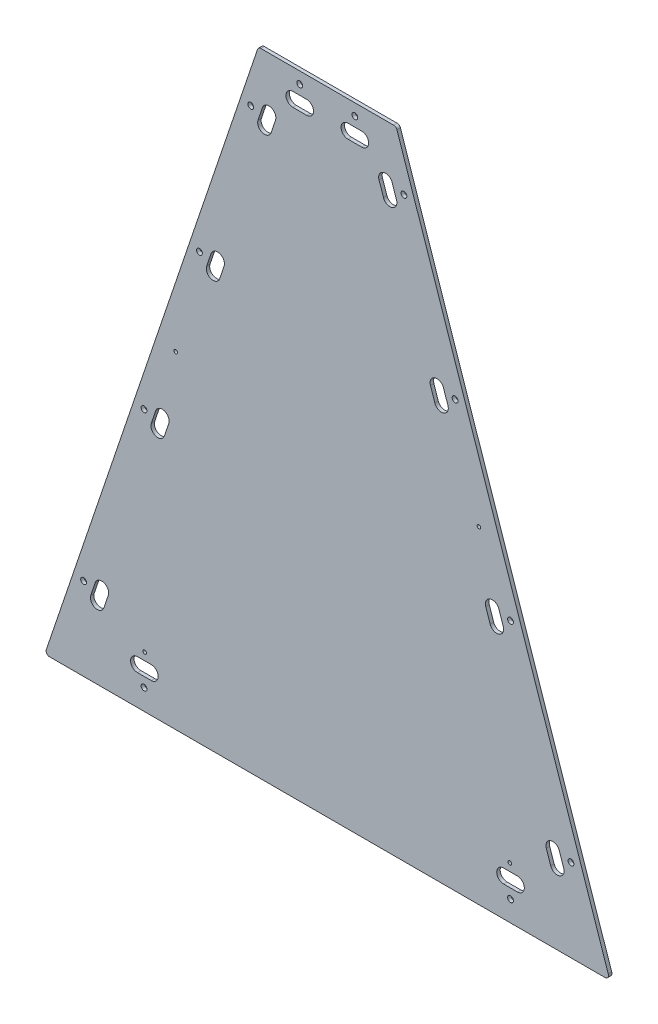
SolidWorks part; units mm, degrees
material "PC High Viscosity"
ref_plane "Front Plane" through (0, 0, 0) normal (0, 0, 1) x (1, 0, 0)
ref_plane "Top Plane" through (0, 0, 0) normal (0, 1, 0) x (1, 0, 0)
ref_plane "Right Plane" through (0, 0, 0) normal (1, 0, 0) x (0, 0, -1)
sketch "Sketch1" plane through (0, 0, 0) normal (0, 0, 1) x (1, 0, 0)
  line L0 (128.5466, 292.9716) -> (382.5466, 292.9716)
  line L5 (382.5466, 292.9716) -> (776.2466, -872.6346)
  line L6 (776.2466, -872.6346) -> (-265.1534, -872.6346)
  line L7 (-265.1534, -872.6346) -> (128.5466, 292.9716)
  line L8 (-168.2075, -740.392) -> (-160.0795, -716.3277) construction
  line L9 (-180.2397, -736.328) -> (-172.1116, -712.2636)
  line L10 (-156.1753, -744.4561) -> (-148.0473, -720.3917)
  line L11 (-94.2317, -804.0546) -> (-68.8317, -804.0546) construction
  line L12 (-94.2317, -791.3546) -> (-68.8317, -791.3546)
  line L13 (-94.2317, -816.7546) -> (-68.8317, -816.7546)
  line L14 (580.5201, -804.0546) -> (605.9201, -804.0546) construction
  line L15 (580.5201, -791.3546) -> (605.9201, -791.3546)
  line L16 (580.5201, -816.7546) -> (605.9201, -816.7546)
  line L17 (-56.7399, -410.3759) -> (-48.6118, -386.3115) construction
  line L18 (-68.7721, -406.3118) -> (-60.644, -382.2474)
  line L19 (-44.7077, -414.4399) -> (-36.5796, -390.3755)
  line L20 (45.2346, -108.4656) -> (53.3626, -84.4012) construction
  line L21 (33.2024, -104.4015) -> (41.3305, -80.3372)
  line L22 (57.2668, -112.5296) -> (65.3948, -88.4652)
  line L29 (139.9814, 172.0464) -> (148.1095, 196.1108) construction
  line L30 (127.9493, 176.1104) -> (136.0773, 200.1748)
  line L31 (152.0136, 167.9823) -> (160.1417, 192.0467)
  line L32 (192.1135, 241.2472) -> (217.5135, 241.2472) construction
  line L33 (192.1135, 253.9472) -> (217.5135, 253.9472)
  line L34 (192.1135, 228.5472) -> (217.5135, 228.5472)
  line L35 (293.6466, 241.2472) -> (319.0466, 241.2472) construction
  line L36 (293.6466, 253.9472) -> (319.0466, 253.9472)
  line L37 (293.6466, 228.5472) -> (319.0466, 228.5472)
  line L38 (371.0972, 172.0897) -> (362.9691, 196.154) construction
  line L39 (359.065, 168.0256) -> (350.9369, 192.09)
  line L40 (383.1294, 176.1537) -> (375.0013, 200.2181)
  line L41 (465.8587, -108.4656) -> (457.7306, -84.4012) construction
  line L42 (453.8265, -112.5296) -> (445.6984, -88.4652)
  line L43 (477.8909, -104.4015) -> (469.7628, -80.3372)
  line L44 (679.3008, -740.392) -> (671.1727, -716.3277) construction
  line L47 (567.8332, -410.3759) -> (559.7051, -386.3115) construction
  line L48 (555.801, -414.4399) -> (547.6729, -390.3755)
  line L49 (579.8654, -406.3118) -> (571.7373, -382.2474)
  line L50 (667.2686, -744.4561) -> (659.1405, -720.3917)
  line L53 (691.333, -736.328) -> (683.2049, -712.2636)
  circle A0 centre (396.7562, 191.3716) radius 5.3578
  circle A1 centre (114.6592, 192.3252) radius 5.3578
  circle A2 centre (-193.5708, -720.2346) radius 5.3578
  circle A4 centre (704.6641, -720.2346) radius 5.3578
  circle A5 centre (491.1275, -88.0284) radius 5.3578
  circle A6 centre (593.2201, -390.2884) radius 5.3578
  circle A7 centre (19.9658, -88.0284) radius 5.3578
  circle A8 centre (-82.1268, -390.2884) radius 5.3578
  circle A9 centre (306.3466, 271.7272) radius 5.3578
  circle A10 centre (204.7466, 271.7272) radius 5.3578
  circle A12 centre (-82.1268, -834.5346) radius 5.3578
  circle A13 centre (593.2201, -834.5346) radius 5.3578
  arc A14 (-180.2397, -736.328) -> (-156.1753, -744.4561) centre (-168.2075, -740.392) ccw
  arc A15 (-148.0473, -720.3917) -> (-172.1116, -712.2636) centre (-160.0795, -716.3277) ccw
  arc A16 (-94.2317, -791.3546) -> (-94.2317, -816.7546) centre (-94.2317, -804.0546) ccw
  arc A17 (-68.8317, -816.7546) -> (-68.8317, -791.3546) centre (-68.8317, -804.0546) ccw
  arc A18 (580.5201, -791.3546) -> (580.5201, -816.7546) centre (580.5201, -804.0546) ccw
  arc A19 (605.9201, -816.7546) -> (605.9201, -791.3546) centre (605.9201, -804.0546) ccw
  arc A20 (-68.7721, -406.3118) -> (-44.7077, -414.4399) centre (-56.7399, -410.3759) ccw
  arc A21 (-36.5796, -390.3755) -> (-60.644, -382.2474) centre (-48.6118, -386.3115) ccw
  arc A22 (33.2024, -104.4015) -> (57.2668, -112.5296) centre (45.2346, -108.4656) ccw
  arc A23 (65.3948, -88.4652) -> (41.3305, -80.3372) centre (53.3626, -84.4012) ccw
  arc A28 (127.9493, 176.1104) -> (152.0136, 167.9823) centre (139.9814, 172.0464) ccw
  arc A29 (160.1417, 192.0467) -> (136.0773, 200.1748) centre (148.1095, 196.1108) ccw
  arc A30 (192.1135, 253.9472) -> (192.1135, 228.5472) centre (192.1135, 241.2472) ccw
  arc A31 (217.5135, 228.5472) -> (217.5135, 253.9472) centre (217.5135, 241.2472) ccw
  arc A32 (293.6466, 253.9472) -> (293.6466, 228.5472) centre (293.6466, 241.2472) ccw
  arc A33 (319.0466, 228.5472) -> (319.0466, 253.9472) centre (319.0466, 241.2472) ccw
  arc A34 (359.065, 168.0256) -> (383.1294, 176.1537) centre (371.0972, 172.0897) ccw
  arc A35 (375.0013, 200.2181) -> (350.9369, 192.09) centre (362.9691, 196.154) ccw
  arc A36 (453.8265, -112.5296) -> (477.8909, -104.4015) centre (465.8587, -108.4656) ccw
  arc A37 (469.7628, -80.3372) -> (445.6984, -88.4652) centre (457.7306, -84.4012) ccw
  arc A40 (555.801, -414.4399) -> (579.8654, -406.3118) centre (567.8332, -410.3759) ccw
  arc A41 (571.7373, -382.2474) -> (547.6729, -390.3755) centre (559.7051, -386.3115) ccw
  arc A44 (667.2686, -744.4561) -> (691.333, -736.328) centre (679.3008, -740.392) ccw
  arc A45 (683.2049, -712.2636) -> (659.1405, -720.3917) centre (671.1727, -716.3277) ccw
  point P24 (-164.1435, -728.3598)
  point P35 (0, 0)
  point P39 (-81.5317, -804.0546)
  point P47 (593.2201, -804.0546)
  point P56 (-52.6759, -398.3437)
  point P62 (204.8135, 241.2472)
  point P65 (49.2986, -96.4334)
  point P93 (144.0455, 184.0786)
  point P106 (306.3466, 241.2472)
  point P115 (367.0332, 184.1219)
  point P125 (461.7947, -96.4334)
  point P136 (675.2368, -728.3598)
  point P140 (563.7691, -398.3437)
  dimension "D5" = 10.7156
  dimension "D6" = 19.05
  dimension "D7" = 17.78
  dimension "D8" = 17.78
  dimension "D9" = 17.78
  dimension "D10" = 17.78
  dimension "D11" = 17.78
  dimension "D12" = 17.78
  dimension "D13" = 38.1
  dimension "D31" = 183.6216
  dimension "D32" = 144.2748
  dimension "D36" = 108.893
  dimension "D37" = 17.78
  dimension "D41" = 76.2669
  dimension "D34" = 776.2012
  dimension "D35" = 25.4
  dimension "D1" = 254
  dimension "D2" = 1230.2998
  dimension "D3" = 1230.2998
  dimension "D4" = 1041.4
  dimension "D14" = 19.05
  dimension "D15" = 683.26
  dimension "D16" = 19.05
  dimension "D17" = 76.2
  dimension "D18" = 381
  dimension "D19" = 683.26
  dimension "D20" = 152.4
  dimension "D21" = 152.4
  dimension "D22" = 19.05
  dimension "D23" = 76.2
  dimension "D24" = 19.05
  dimension "D25" = 381
  dimension "D26" = 101.6
  dimension "D27" = 19.05
  dimension "D28" = 19.05
  dimension "D29" = 19.05
  dimension "D30" = 101.6
  dimension "D33" = 474.291
  dimension "D38" = 38.1
  dimension "D39" = 25.4
  dimension "D40" = 17.78
  dimension "D42" = 17.78
  dimension "D43" = 108.8497
  dimension "D47" = 17.78
  dimension "D52" = 17.78
  dimension "D53" = 17.78
  dimension "D56" = 21.2444
  dimension "D57" = 21.2444
extrude "Boss-Extrude1" add sketch "Sketch1" along normal blind 6.35 contours L7 L6 L5 L0 A29 L31 A28 L30 A23 L22 A22 L21 A21 L19 A20 L18 A19 L16 A18 L15 A17 L13 A16 L12 A15 L10 A14 L9 A13 A12 A10 A9 A8 A7 A6 A5 region at (255.5456, -410.7622, 0)
fillet "Fillet1" radius 6.35 4 edges at (-265.1534, -872.6346, 3.175) (776.2466, -872.6346, 3.175) (382.5466, 292.9716, 3.175) (128.5466, 292.9716, 3.175)
sketch "Sketch2" plane through (0, 0, 6.35) normal (0, 0, 1) x (1, 0, 0)
  line L0 (255.5466, -872.6346) -> (255.5466, 292.9716) construction
  line L1 (767.3994, -872.6346) -> (-256.3061, -872.6346) construction
  line L2 (133.1043, 292.9716) -> (377.989, 292.9716) construction
  line L3 (91.6472, -808.2573) -> (67.9728, -842.0678)
  line L4 (443.1205, -842.0678) -> (419.4461, -808.2573)
  arc A0 (91.6472, -808.2573) -> (419.4461, -808.2573) centre (255.5466, -574.1846) cw
  arc A1 (67.9728, -842.0678) -> (443.1205, -842.0678) centre (255.5466, -574.1846) cw
  point P0 (255.5466, -288.4346)
  dimension "D3" = 298.45
  dimension "D1" = 41.275
  dimension "D2" = 584.2
  dimension "D4" = 70
sketch "Sketch4" [suppressed] plane through (0, 0, 6.35) normal (0, 0, 1) x (1, 0, 0)
  line L0 (414.1087, -288.4346) -> (255.5466, -288.4346)
  line L13 (414.1087, -288.4346) -> (572.6707, -563.0721)
  line L14 (572.6707, -563.0721) -> (414.1087, -837.7096)
  line L15 (767.3994, -872.6346) -> (-256.3061, -872.6346) construction
  line L16 (255.5466, -288.4346) -> (255.5466, -872.6346) construction
  line L17 (437.9388, -247.1596) -> (255.5466, -247.1596)
  line L18 (437.9388, -247.1596) -> (620.331, -563.0721)
  line L19 (620.331, -563.0721) -> (449.8539, -858.3471)
  line L20 (449.8539, -858.3471) -> (414.1087, -837.7096)
  line L21 (61.2394, -858.3471) -> (96.9846, -837.7096)
  line L22 (-109.2377, -563.0721) -> (61.2394, -858.3471)
  line L23 (73.1545, -247.1596) -> (-109.2377, -563.0721)
  line L24 (73.1545, -247.1596) -> (255.5466, -247.1596)
  line L25 (-61.5774, -563.0721) -> (96.9846, -837.7096)
  line L26 (96.9846, -288.4346) -> (-61.5774, -563.0721)
  line L27 (96.9846, -288.4346) -> (255.5466, -288.4346)
  line L28 (414.1087, -837.7096) -> (96.9846, -837.7096) construction
  dimension "D1" = 309.5625
  dimension "D2" = 317.1241
  dimension "D3" = 120
  dimension "D4" = 120
  dimension "D5" = 41.275
extrude "Cut-Extrude1" [suppressed] cut sketch "Sketch2" against normal through all
extrude "Cut-Extrude2" [suppressed] cut sketch "Sketch4" against normal through all
sketch "Sketch5" [suppressed] plane through (0, 0, 6.35) normal (0, 0, 1) x (1, 0, 0)
  line L0 (57.2668, -112.5296) -> (65.3948, -88.4652) construction
  line L1 (33.2024, -104.4015) -> (41.3305, -80.3372) construction
  line L2 (-44.7077, -414.4399) -> (-36.5796, -390.3755) construction
  line L3 (-68.7721, -406.3118) -> (-60.644, -382.2474) construction
  line L4 (-180.2397, -736.328) -> (-172.1116, -712.2636) construction
  line L5 (-156.1753, -744.4561) -> (-148.0473, -720.3917) construction
  line L6 (-94.2317, -816.7546) -> (-68.8317, -816.7546) construction
  line L7 (-94.2317, -791.3546) -> (-68.8317, -791.3546) construction
  line L8 (57.2668, -112.5296) -> (65.3948, -88.4652)
  line L9 (33.2024, -104.4015) -> (41.3305, -80.3372)
  line L10 (-44.7077, -414.4399) -> (-36.5796, -390.3755)
  line L11 (-68.7721, -406.3118) -> (-60.644, -382.2474)
  line L12 (-180.2397, -736.328) -> (-172.1116, -712.2636)
  line L13 (-156.1753, -744.4561) -> (-148.0473, -720.3917)
  line L14 (-94.2317, -816.7546) -> (-68.8317, -816.7546)
  line L15 (-94.2317, -791.3546) -> (-68.8317, -791.3546)
  line L16 (192.1135, 228.5472) -> (217.5135, 228.5472) construction
  line L17 (192.1135, 253.9472) -> (217.5135, 253.9472) construction
  line L18 (152.0136, 167.9823) -> (160.1417, 192.0467) construction
  line L19 (127.9493, 176.1104) -> (136.0773, 200.1748) construction
  line L20 (192.1135, 228.5472) -> (217.5135, 228.5472)
  line L21 (192.1135, 253.9472) -> (217.5135, 253.9472)
  line L22 (152.0136, 167.9823) -> (160.1417, 192.0467)
  line L23 (127.9493, 176.1104) -> (136.0773, 200.1748)
  line L24 (255.5466, 292.9716) -> (255.5466, -872.6346) construction
  line L37 (359.065, 168.0256) -> (350.9369, 192.09) construction
  line L38 (383.1294, 176.1537) -> (375.0013, 200.2181) construction
  line L39 (293.6466, 228.5472) -> (319.0466, 228.5472) construction
  line L40 (293.6466, 253.9472) -> (319.0466, 253.9472) construction
  line L41 (359.065, 168.0256) -> (350.9369, 192.09)
  line L42 (383.1294, 176.1537) -> (375.0013, 200.2181)
  line L43 (293.6466, 228.5472) -> (319.0466, 228.5472)
  line L44 (293.6466, 253.9472) -> (319.0466, 253.9472)
  line L45 (453.8265, -112.5296) -> (445.6984, -88.4652) construction
  line L46 (477.8909, -104.4015) -> (469.7628, -80.3372) construction
  line L47 (453.8265, -112.5296) -> (445.6984, -88.4652)
  line L48 (477.8909, -104.4015) -> (469.7628, -80.3372)
  line L49 (555.801, -414.4399) -> (547.6729, -390.3755) construction
  line L50 (579.8654, -406.3118) -> (571.7373, -382.2474) construction
  line L51 (555.801, -414.4399) -> (547.6729, -390.3755)
  line L52 (579.8654, -406.3118) -> (571.7373, -382.2474)
  line L53 (667.2686, -744.4561) -> (659.1405, -720.3917) construction
  line L54 (691.333, -736.328) -> (683.2049, -712.2636) construction
  line L55 (667.2686, -744.4561) -> (659.1405, -720.3917)
  line L56 (691.333, -736.328) -> (683.2049, -712.2636)
  line L57 (580.5201, -791.3546) -> (605.9201, -791.3546) construction
  line L58 (580.5201, -816.7546) -> (605.9201, -816.7546) construction
  line L59 (580.5201, -791.3546) -> (605.9201, -791.3546)
  line L60 (580.5201, -816.7546) -> (605.9201, -816.7546)
  arc A0 (33.2024, -104.4015) -> (57.2668, -112.5296) centre (45.2346, -108.4656) ccw construction
  arc A1 (65.3948, -88.4652) -> (41.3305, -80.3372) centre (53.3626, -84.4012) ccw construction
  circle A2 centre (19.9658, -88.0284) radius 5.3578 construction
  arc A3 (-68.7721, -406.3118) -> (-44.7077, -414.4399) centre (-56.7399, -410.3759) ccw construction
  circle A4 centre (-82.1268, -390.2884) radius 5.3578 construction
  arc A5 (-36.5796, -390.3755) -> (-60.644, -382.2474) centre (-48.6118, -386.3115) ccw construction
  circle A6 centre (-193.5708, -720.2346) radius 5.3578 construction
  arc A7 (-148.0473, -720.3917) -> (-172.1116, -712.2636) centre (-160.0795, -716.3277) ccw construction
  arc A8 (-180.2397, -736.328) -> (-156.1753, -744.4561) centre (-168.2075, -740.392) ccw construction
  arc A9 (-94.2317, -791.3546) -> (-94.2317, -816.7546) centre (-94.2317, -804.0546) ccw construction
  arc A10 (-68.8317, -816.7546) -> (-68.8317, -791.3546) centre (-68.8317, -804.0546) ccw construction
  circle A11 centre (-82.1268, -834.5346) radius 5.3578 construction
  arc A12 (33.2024, -104.4015) -> (57.2668, -112.5296) centre (45.2346, -108.4656) ccw
  arc A13 (65.3948, -88.4652) -> (41.3305, -80.3372) centre (53.3626, -84.4012) ccw
  circle A14 centre (19.9658, -88.0284) radius 5.3578
  arc A15 (-68.7721, -406.3118) -> (-44.7077, -414.4399) centre (-56.7399, -410.3759) ccw
  circle A16 centre (-82.1268, -390.2884) radius 5.3578
  arc A17 (-36.5796, -390.3755) -> (-60.644, -382.2474) centre (-48.6118, -386.3115) ccw
  circle A18 centre (-193.5708, -720.2346) radius 5.3578
  arc A19 (-148.0473, -720.3917) -> (-172.1116, -712.2636) centre (-160.0795, -716.3277) ccw
  arc A20 (-180.2397, -736.328) -> (-156.1753, -744.4561) centre (-168.2075, -740.392) ccw
  arc A21 (-94.2317, -791.3546) -> (-94.2317, -816.7546) centre (-94.2317, -804.0546) ccw
  arc A22 (-68.8317, -816.7546) -> (-68.8317, -791.3546) centre (-68.8317, -804.0546) ccw
  circle A23 centre (-82.1268, -834.5346) radius 5.3578
  arc A24 (217.5135, 228.5472) -> (217.5135, 253.9472) centre (217.5135, 241.2472) ccw construction
  arc A25 (192.1135, 253.9472) -> (192.1135, 228.5472) centre (192.1135, 241.2472) ccw construction
  circle A26 centre (204.7466, 271.7272) radius 5.3578 construction
  arc A27 (127.9493, 176.1104) -> (152.0136, 167.9823) centre (139.9814, 172.0464) ccw construction
  arc A28 (160.1417, 192.0467) -> (136.0773, 200.1748) centre (148.1095, 196.1108) ccw construction
  circle A29 centre (114.6592, 192.3252) radius 5.3578 construction
  arc A30 (217.5135, 228.5472) -> (217.5135, 253.9472) centre (217.5135, 241.2472) ccw
  arc A31 (192.1135, 253.9472) -> (192.1135, 228.5472) centre (192.1135, 241.2472) ccw
  circle A32 centre (204.7466, 271.7272) radius 5.3578
  arc A33 (127.9493, 176.1104) -> (152.0136, 167.9823) centre (139.9814, 172.0464) ccw
  arc A34 (160.1417, 192.0467) -> (136.0773, 200.1748) centre (148.1095, 196.1108) ccw
  circle A35 centre (114.6592, 192.3252) radius 5.3578
  circle A54 centre (306.3466, 271.7272) radius 5.3578 construction
  circle A55 centre (306.3466, 271.7272) radius 5.3578
  circle A56 centre (396.7562, 191.3716) radius 5.3578 construction
  arc A57 (359.065, 168.0256) -> (383.1294, 176.1537) centre (371.0972, 172.0897) ccw construction
  arc A58 (375.0013, 200.2181) -> (350.9369, 192.09) centre (362.9691, 196.154) ccw construction
  arc A59 (293.6466, 253.9472) -> (293.6466, 228.5472) centre (293.6466, 241.2472) ccw construction
  arc A60 (319.0466, 228.5472) -> (319.0466, 253.9472) centre (319.0466, 241.2472) ccw construction
  circle A61 centre (396.7562, 191.3716) radius 5.3578
  arc A62 (359.065, 168.0256) -> (383.1294, 176.1537) centre (371.0972, 172.0897) ccw
  arc A63 (375.0013, 200.2181) -> (350.9369, 192.09) centre (362.9691, 196.154) ccw
  arc A64 (293.6466, 253.9472) -> (293.6466, 228.5472) centre (293.6466, 241.2472) ccw
  arc A65 (319.0466, 228.5472) -> (319.0466, 253.9472) centre (319.0466, 241.2472) ccw
  arc A66 (453.8265, -112.5296) -> (477.8909, -104.4015) centre (465.8587, -108.4656) ccw construction
  arc A67 (469.7628, -80.3372) -> (445.6984, -88.4652) centre (457.7306, -84.4012) ccw construction
  circle A68 centre (491.1275, -88.0284) radius 5.3578 construction
  arc A69 (453.8265, -112.5296) -> (477.8909, -104.4015) centre (465.8587, -108.4656) ccw
  arc A70 (469.7628, -80.3372) -> (445.6984, -88.4652) centre (457.7306, -84.4012) ccw
  circle A71 centre (491.1275, -88.0284) radius 5.3578
  arc A72 (555.801, -414.4399) -> (579.8654, -406.3118) centre (567.8332, -410.3759) ccw construction
  circle A73 centre (593.2201, -390.2884) radius 5.3578 construction
  arc A74 (571.7373, -382.2474) -> (547.6729, -390.3755) centre (559.7051, -386.3115) ccw construction
  arc A75 (555.801, -414.4399) -> (579.8654, -406.3118) centre (567.8332, -410.3759) ccw
  circle A76 centre (593.2201, -390.2884) radius 5.3578
  arc A77 (571.7373, -382.2474) -> (547.6729, -390.3755) centre (559.7051, -386.3115) ccw
  arc A78 (667.2686, -744.4561) -> (691.333, -736.328) centre (679.3008, -740.392) ccw construction
  arc A79 (683.2049, -712.2636) -> (659.1405, -720.3917) centre (671.1727, -716.3277) ccw construction
  circle A80 centre (704.6641, -720.2346) radius 5.3578 construction
  arc A81 (667.2686, -744.4561) -> (691.333, -736.328) centre (679.3008, -740.392) ccw
  arc A82 (683.2049, -712.2636) -> (659.1405, -720.3917) centre (671.1727, -716.3277) ccw
  circle A83 centre (704.6641, -720.2346) radius 5.3578
  arc A84 (605.9201, -816.7546) -> (605.9201, -791.3546) centre (605.9201, -804.0546) ccw construction
  circle A85 centre (593.2201, -834.5346) radius 5.3578 construction
  arc A86 (580.5201, -791.3546) -> (580.5201, -816.7546) centre (580.5201, -804.0546) ccw construction
  arc A87 (605.9201, -816.7546) -> (605.9201, -791.3546) centre (605.9201, -804.0546) ccw
  circle A88 centre (593.2201, -834.5346) radius 5.3578
  arc A89 (580.5201, -791.3546) -> (580.5201, -816.7546) centre (580.5201, -804.0546) ccw
extrude "Boss-Extrude2" [suppressed] add sketch "Sketch5" against normal up to surface (6.35 mm away) up to face at (675.2368, -728.3598, 0)
sketch "Sketch6" plane through (0, 0, 6.35) normal (0, 0, 1) x (1, 0, 0)
  line L0 (255.5466, 292.9716) -> (255.5466, -872.6346) construction
  line L1 (133.1043, 292.9716) -> (377.989, 292.9716) construction
  line L2 (767.3994, -872.6346) -> (-256.3061, -872.6346) construction
  point P0 (-81.0034, -777.3846)
  point P1 (-23.8534, -269.3846)
  point P2 (534.9466, -269.3846)
  point P3 (592.0966, -777.3846)
  point P10 (0, 0)
  point P11 (0, 0)
  point P12 (102.4644, -510.1037)
  dimension "D1" = 673.1
  dimension "D2" = 336.55
  dimension "D3" = 558.8
  dimension "D4" = 279.4
  dimension "D5" = 508
  dimension "D6" = 95.25
hole_wizard "17/64 (0.26563) Diameter Hole1" positions "Sketch7" profile "Sketch8" hole size "17/64" standard "ANSI Inch" end condition through all
sketch "Sketch7" plane through (0, 0, 6.35) normal (0, 0, 1) x (1, 0, 0)
  point P0 (-23.8534, -269.3846)
  point P3 (534.9466, -269.3846)
  point P6 (592.0966, -777.3846)
  point P9 (-81.0034, -777.3846)
sketch "Sketch8" plane through (-23.8534, -269.3846, 6.35) normal (1, 0, 0) x (0, -1, 0)
  line L0 (0, 0) -> (0, 6.35)
  line L1 (0, 6.35) -> (3.3735, 6.35)
  line L2 (3.3735, 6.35) -> (3.3735, 0)
  line L5 (3.3735, 0) -> (0, 0)
  line L11 (0, -6.35) -> (0, 107.95) construction
  dimension "Thru Hole Dia." = 6.747
  dimension "Thru Hole Depth" = 6.35
equation "\"D2@Sketch6\"=\"D1@Sketch6\"/2"
equation "\"D4@Sketch6\"=\"D3@Sketch6\"/2"
